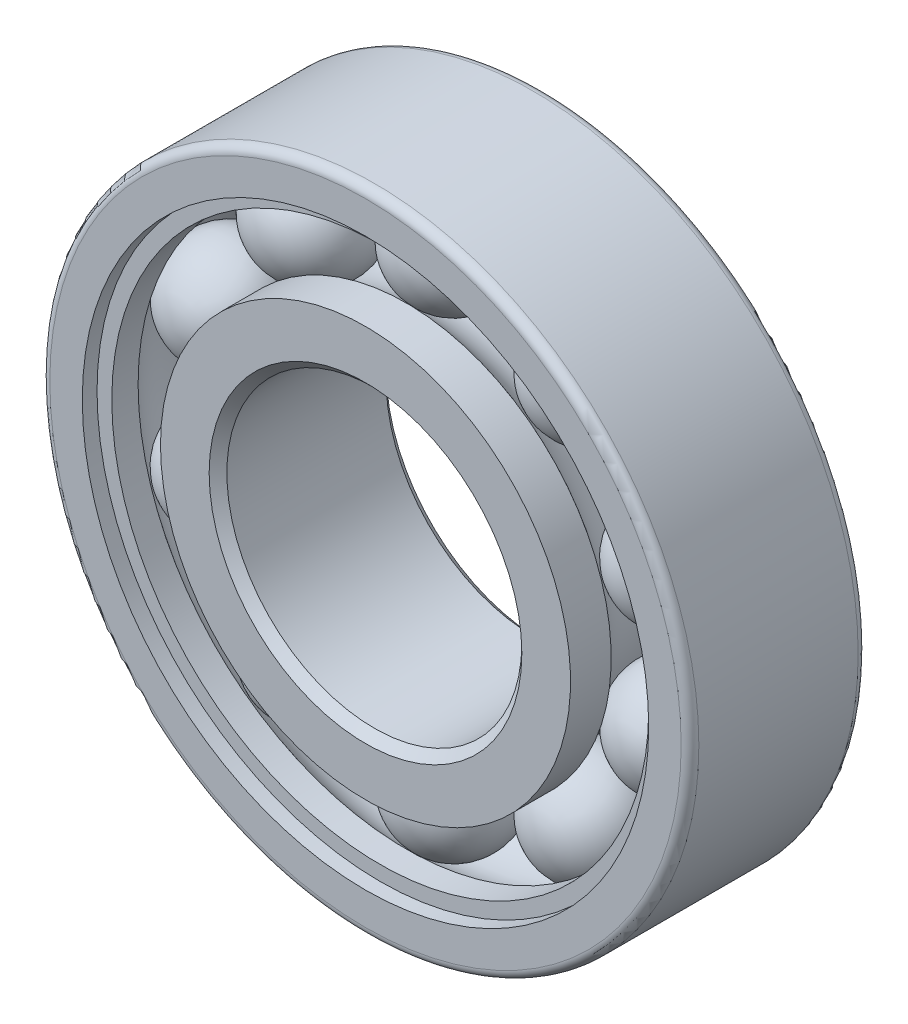
SolidWorks part; units mm, degrees
ref_plane "Front Plane" through (0, 0, 0) normal (0, 0, 1) x (1, 0, 0)
ref_plane "Top Plane" through (0, 0, 0) normal (0, 1, 0) x (1, 0, 0)
ref_plane "Right Plane" through (0, 0, 0) normal (1, 0, 0) x (0, 0, -1)
sketch "Sketch6" plane through (0, 0, 0) normal (1, 0, 0) x (0, 0, -1)
  line L0 (0, 10.05) -> (0, 0) construction
  line L1 (3, 11) -> (-3, 11)
  line L2 (3, 11) -> (3, 9.1)
  line L3 (3, 9.1) -> (-3, 9.1)
  line L4 (-3, 11) -> (-3, 9.1)
  line L5 (3, 11) -> (-3, 9.1) construction
  line L6 (3, 9.1) -> (-3, 11) construction
  line L7 (3, 6.95) -> (-3, 6.95)
  line L8 (3, 6.95) -> (3, 5)
  line L9 (3, 5) -> (-3, 5)
  line L10 (-3, 6.95) -> (-3, 5)
  line L11 (3, 6.95) -> (-3, 5) construction
  line L12 (3, 5) -> (-3, 6.95) construction
  line L13 (0, 0) -> (-4.8837, 0) construction
  circle A0 centre (0, 8.015) radius 1.9401
  point P0 (0, 10.05)
  point P5 (0, 5.975)
  dimension "D1" = 6
  dimension "D2" = 5
  dimension "D3" = 11
  dimension "D4" = 6.95
  dimension "D5" = 9.1
revolve "Revolve2" add sketch "Sketch6" angle 360 about L13 region at (0, 10.1727, 0) region at (0, 5.8479, 0)
ref_axis "Axis1" through (0, 0, 3) along (0, 0, -1)
sketch "Sketch9" plane through (0, 0, 0) normal (1, 0, 0) x (0, 0, -1)
  line L0 (-1.9, 8.01) -> (1.9, 8.01)
  circle A0 centre (0, 8.01) radius 1.9
  dimension "D1" = 8.01
  dimension "D2" = 3.8
revolve "Revolve3" add sketch "Sketch9" angle 360 about L0 region at (0, 8.8164, 0)
pattern_circular "CirPattern3" count 10 over 360 about axis through (0, 0, 3) along (0, 0, -1) of bodies 104
sketch "Sketch10" plane through (0, 0, -3) normal (0, 0, -1) x (-1, 0, 0)
  circle A0 centre (0, 0) radius 9.1 construction
  circle A1 centre (0, 0) radius 9.1
  circle A2 centre (0, 0) radius 9.6
  dimension "D1" = 0.5
extrude "Cut-Extrude1" cut sketch "Sketch10" against normal blind 0.5
mirror "Mirror1" about plane through (0, 0, 0) normal (0, 0, 1) of "Cut-Extrude1"
fillet "Fillet1" radius 0.3 2 edges at (-11, 0, -3) (-11, 0, 3)
chamfer "Chamfer1" distance 0.3 angle 45 2 edges at (-5, 0, -3) (-5, 0, 3)
